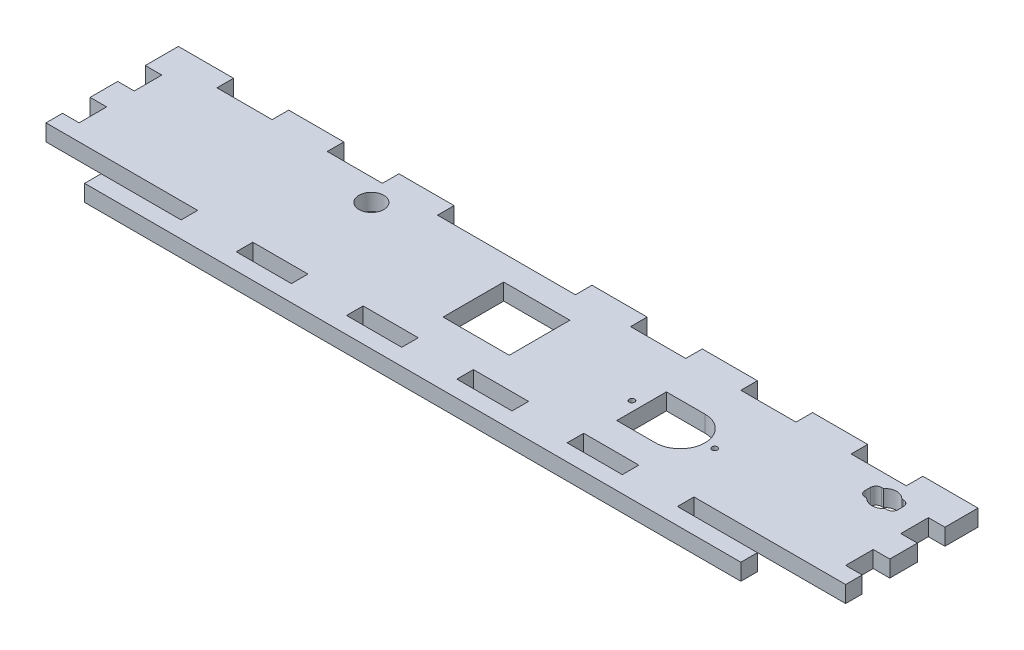
SolidWorks part; units mm, degrees
material "Maple"
ref_plane "Front Plane" through (0, 0, 0) normal (0, 0, 1) x (1, 0, 0)
ref_plane "Top Plane" through (0, 0, 0) normal (0, 1, 0) x (1, 0, 0)
ref_plane "Right Plane" through (0, 0, 0) normal (1, 0, 0) x (0, 0, -1)
sketch "Sketch1" plane through (0, 0, 0) normal (0, 1, 0) x (1, 0, 0)
  line L1 (0, 0) -> (145, 0)
  line L2 (0, 0) -> (0, -21)
  line L3 (0, -21) -> (145, -21)
  line L4 (145, 0) -> (145, -21)
  dimension "D1" = 145
  dimension "D2" = 21
extrude "Boss-Extrude1" add sketch "Sketch1" along normal blind 3
sketch "Sketch2" plane through (0, 3, 0) normal (0, 1, 0) x (1, 0, 0)
  line L0 (72.5, -21) -> (72.5, 0) construction
  line L1 (0, -21) -> (145, -21) construction
  line L2 (145, 0) -> (0, 0) construction
  line L4 (66.5, -4.5) -> (78.5, -4.5)
  line L5 (66.5, -4.5) -> (66.5, -15.5)
  line L6 (66.5, -15.5) -> (78.5, -15.5)
  line L7 (78.5, -4.5) -> (78.5, -15.5)
  line L8 (66.5, -4.5) -> (78.5, -15.5) construction
  line L9 (66.5, -15.5) -> (78.5, -4.5) construction
  point P6 (72.5, -10)
  dimension "D1" = 4.5
  dimension "D2" = 11
  dimension "D3" = 12
extrude "Cut-Extrude1" cut sketch "Sketch2" against normal through all
sketch "Sketch3" plane through (0, 3, 0) normal (0, 1, 0) x (1, 0, 0)
  line L0 (145, 0) -> (0, 0) construction
  line L1 (0, 0) -> (0, -21) construction
  line L3 (145, -21) -> (145, 0) construction
  circle A0 centre (42, -4) radius 2.25
  circle A1 centre (135, -4) radius 2.25
  dimension "D1" = 4.5
  dimension "D4" = 4.5
  dimension "D5" = 4
  dimension "D2" = 42
  dimension "D3" = 4
  dimension "D6" = 10
extrude "Cut-Extrude2" cut sketch "Sketch3" against normal through all
sketch "Sketch4" plane through (0, 3, 0) normal (0, 1, 0) x (1, 0, 0)
  line L0 (98.5, -11.5) -> (110, -11.5) construction
  line L1 (98.5, -16) -> (110, -16)
  line L2 (98.5, -16) -> (98.5, -7)
  line L3 (98.5, -7) -> (110, -7)
  line L4 (110, -16) -> (110, -7)
  line L5 (0, -21) -> (145, -21) construction
  line L6 (145, -21) -> (145, 0) construction
  line L7 (104.25, -16) -> (104.25, -7) construction
  circle A0 centre (105.5, -11.5) radius 4.5
  circle A1 centre (96.75, -11.5) radius 0.5
  circle A2 centre (111.75, -11.5) radius 0.5
  dimension "D5" = 1
  dimension "D6" = 1
  dimension "D1" = 9
  dimension "D2" = 11.5
  dimension "D3" = 5
  dimension "D4" = 35
  dimension "D7" = 15
  dimension "D8" = 7.5
extrude "Cut-Extrude3" cut sketch "Sketch4" against normal through all contours L0 A0 | A0 L3 L2 L1 | A1 | A2 region at (100.3784, 3, 11.5) region at (105.5, 3, 11.5) region at (96.75, 3, 11.5) region at (111.75, 3, 11.5)
sketch "Sketch5" plane through (0, 3, 0) normal (0, 1, 0) x (1, 0, 0)
  line L0 (72.5, 0) -> (72.5, -21) construction
  line L1 (145, 0) -> (0, 0) construction
  line L2 (0, -21) -> (145, -21) construction
  line L4 (67.5, -21) -> (77.5, -21)
  line L5 (67.5, -21) -> (67.5, -24)
  line L6 (67.5, -24) -> (77.5, -24)
  line L7 (77.5, -21) -> (77.5, -24)
  line L8 (67.5, -21) -> (77.5, -24) construction
  line L9 (67.5, -24) -> (77.5, -21) construction
  point P6 (72.5, -22.5)
  dimension "D1" = 3
  dimension "D2" = 10
extrude "Boss-Extrude2" add sketch "Sketch5" against normal through all
pattern_linear "LPattern1" count 4 spacing 20 along (-1, 0, 0) count 4 spacing 20 along (1, 0, 0) of "Boss-Extrude2" pattern seed only yes
sketch "Sketch6" plane through (0, 3, 0) normal (0, 1, 0) x (1, 0, 0)
  line L0 (7.5, -24) -> (17.5, -24) construction
  line L1 (0, -24) -> (145, -24)
  line L2 (0, -24) -> (0, -27)
  line L3 (0, -27) -> (145, -27)
  line L4 (145, -24) -> (145, -27)
  line L5 (0, 0) -> (0, -21) construction
  line L6 (145, -21) -> (145, 0) construction
  dimension "D1" = 3
extrude "Boss-Extrude3" add sketch "Sketch6" against normal through all
sketch "Sketch8" plane through (0, 0, 0) normal (0, -1, 0) x (-1, 0, 0)
  line L1 (-7.5, -24) -> (-17.5, -24)
  line L2 (-7.5, -24) -> (-7.5, -21)
  line L3 (-7.5, -21) -> (-17.5, -21)
  line L4 (-17.5, -24) -> (-17.5, -21)
  line L5 (-137.5, -24) -> (-127.5, -24)
  line L6 (-137.5, -24) -> (-137.5, -21)
  line L7 (-137.5, -21) -> (-127.5, -21)
  line L8 (-127.5, -24) -> (-127.5, -21)
extrude "Cut-Extrude4" cut sketch "Sketch8" against normal through all
sketch "Sketch9" plane through (0, 3, 0) normal (0, 1, 0) x (1, 0, 0)
  line L0 (0, 0) -> (0, -21) construction
  line L1 (3, -13) -> (0, -13)
  line L2 (3, -13) -> (3, -18)
  line L3 (3, -18) -> (0, -18)
  line L4 (0, -13) -> (0, -18)
  line L5 (0, 0) -> (0, -21) construction
  line L6 (145, -21) -> (145, 0) construction
  line L7 (3, -3) -> (0, -3)
  line L8 (3, -3) -> (3, -8)
  line L9 (3, -8) -> (0, -8)
  line L10 (0, -3) -> (0, -8)
  line L11 (142, -13) -> (145, -13)
  line L12 (142, -13) -> (142, -18)
  line L13 (142, -18) -> (145, -18)
  line L14 (145, -13) -> (145, -18)
  line L15 (145, 0) -> (0, 0) construction
  line L16 (142, -3) -> (145, -3)
  line L17 (142, -3) -> (142, -8)
  line L18 (142, -8) -> (145, -8)
  line L19 (145, -3) -> (145, -8)
  dimension "D1" = 3
  dimension "D2" = 5
  dimension "D3" = 5
  dimension "D4" = 5
  dimension "D5" = 3
extrude "Cut-Extrude5" cut sketch "Sketch9" against normal through all
sketch "Sketch10" plane through (0, 0, 0) normal (0, -1, 0) x (-1, 0, 0)
  line L0 (-27.5, -24) -> (0, -24) construction
  line L1 (0, -27) -> (-13, -27)
  line L2 (0, -27) -> (0, -24)
  line L3 (0, -24) -> (-13, -24)
  line L4 (-13, -27) -> (-13, -24)
  line L5 (-145, -24) -> (-117.5, -24) construction
  line L6 (-145, -27) -> (-132, -27)
  line L7 (-145, -27) -> (-145, -24)
  line L8 (-145, -24) -> (-132, -24)
  line L9 (-132, -27) -> (-132, -24)
  dimension "D1" = 13
extrude "Cut-Extrude6" cut sketch "Sketch10" against normal through all
sketch "Sketch11" plane through (0, 0, 0) normal (0, -1, 0) x (-1, 0, 0)
  line L1 (0, 0) -> (-10, 0)
  line L2 (0, 0) -> (0, 3)
  line L3 (0, 3) -> (-10, 3)
  line L4 (-10, 0) -> (-10, 3)
  dimension "D1" = 10
  dimension "D2" = 3
extrude "Boss-Extrude4" add sketch "Sketch11" against normal through all
pattern_linear "LPattern2" count 3 spacing 20 along (1, 0, 0) of "Boss-Extrude4"
sketch "Sketch12" plane through (0, 0, 0) normal (0, -1, 0) x (-1, 0, 0)
  line L1 (-145, 0) -> (-135, 0)
  line L2 (-145, 0) -> (-145, 3)
  line L3 (-145, 3) -> (-135, 3)
  line L4 (-135, 0) -> (-135, 3)
  dimension "D1" = 3
  dimension "D2" = 10
extrude "Boss-Extrude5" add sketch "Sketch12" against normal through all
pattern_linear "LPattern3" count 4 spacing 20 along (-1, 0, 0) of "Boss-Extrude5"
sketch "Sketch13" plane through (0, 3, 0) normal (0, 1, 0) x (1, 0, 0)
  line L0 (132.75, -4) -> (137.25, -4) construction
  line L1 (135, -1.75) -> (135, -6.25) construction
  line L2 (132, -2.5) -> (138, -2.5)
  line L3 (132, -2.5) -> (132, -5.5)
  line L4 (132, -5.5) -> (138, -5.5)
  line L5 (138, -2.5) -> (138, -5.5)
  line L6 (132, -2.5) -> (138, -5.5) construction
  line L7 (132, -5.5) -> (138, -2.5) construction
  circle A0 centre (135, -4) radius 2.25 construction
  point P4 (135, -4)
  point P9 (135, -3.3153)
  dimension "D1" = 3
  dimension "D2" = 6
extrude "Cut-Extrude7" cut sketch "Sketch13" against normal through all
fillet "Fillet1" radius 1 4 edges at (138, 1.5, 5.5) (138, 1.5, 2.5) (132, 1.5, 5.5) (132, 1.5, 2.5)
equation "\"D6@Sketch4\"=\"D5@Sketch4\""
equation "\"D8@Sketch4\"=\"D7@Sketch4\"/2"
